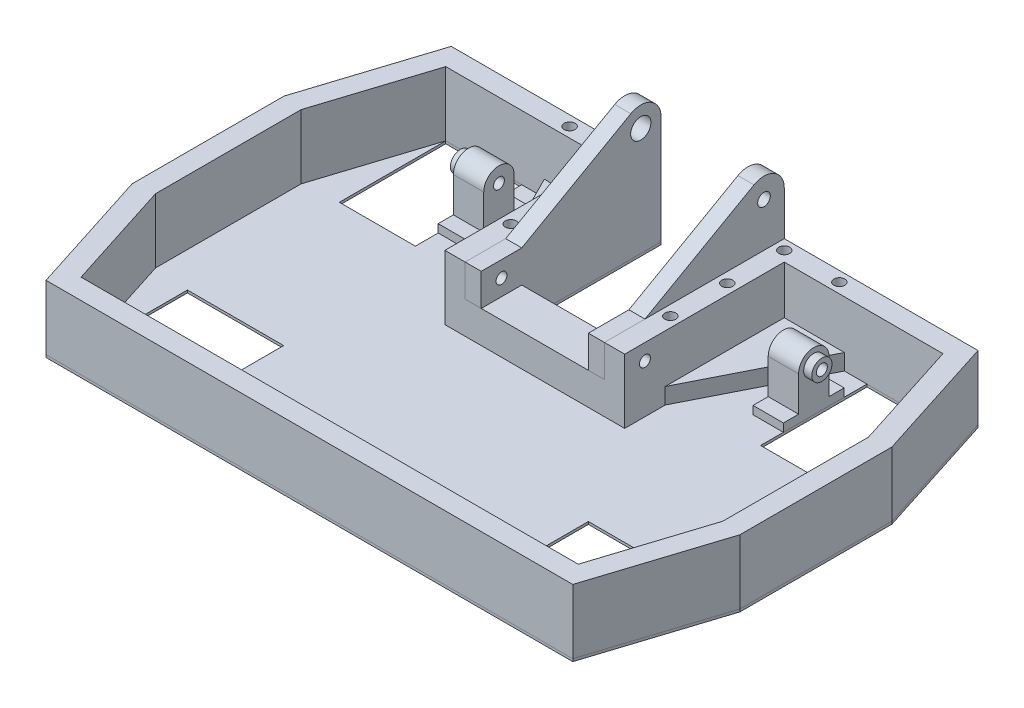
SolidWorks part; units mm, degrees
ref_plane "Front Plane" through (0, 0, 0) normal (0, 0, 1) x (1, 0, 0)
ref_plane "Top Plane" through (0, 0, 0) normal (0, 1, 0) x (1, 0, 0)
ref_plane "Right Plane" through (0, 0, 0) normal (1, 0, 0) x (0, 0, -1)
sketch "Sketch1" plane through (0, 0, 0) normal (0, 1, 0) x (1, 0, 0)
  line L0 (-27.5, 0) -> (-104, 0)
  line L1 (-104, 0) -> (-120, -50)
  line L2 (-120, -50) -> (-120, -110)
  line L3 (-120, -110) -> (-104, -160)
  line L4 (-104, -160) -> (104, -160)
  line L5 (104, -160) -> (120, -110)
  line L6 (120, -110) -> (120, -50)
  line L7 (120, -50) -> (104, 0)
  line L8 (104, 0) -> (27.5, 0)
  line L9 (-27.5, 0) -> (-27.5, -55)
  line L10 (27.5, 0) -> (27.5, -55)
  line L11 (-27.5, -55) -> (27.5, -55)
  line L13 (0, -51.275) -> (0, 31.275) construction
  point P16 (0, -160)
  point P17 (0, -10)
  dimension "D1" = 240
  dimension "D2" = 160
  dimension "D3" = 60
  dimension "D4" = 16
  dimension "D5" = 55
  dimension "D6" = 55
  dimension "D8" = 10
  dimension "D9" = 82.55
extrude "Extrude-Thin1" add sketch "Sketch1" along normal blind 25.4 thin thin type one direction reverse wall 8
sketch "Sketch19" plane through (0, 0, 0) normal (0, 0, -1) x (-1, 0, 0)
  line L0 (-21.15, 0) -> (-21.15, 50.8)
  line L1 (-27.5, 0) -> (27.5, 0) construction
  line L2 (-21.15, 50.8) -> (-27.5, 50.8)
  line L3 (-27.5, 50.8) -> (-27.5, 6.35)
  line L4 (-27.5, 6.35) -> (-59.25, 6.35)
  line L5 (-59.25, 6.35) -> (-59.25, 0)
  line L6 (-104, 0) -> (-27.5, 0) construction
  line L7 (-59.25, 0) -> (-21.15, 0)
  line L8 (-27.5, 25.4) -> (-27.5, 0) construction
  line L9 (0, 0) -> (0, 43.8117) construction
  line L10 (59.25, 0) -> (21.15, 0)
  line L11 (59.25, 6.35) -> (59.25, 0)
  line L12 (27.5, 6.35) -> (59.25, 6.35)
  line L13 (27.5, 50.8) -> (27.5, 6.35)
  line L14 (21.15, 50.8) -> (27.5, 50.8)
  line L15 (21.15, 0) -> (21.15, 50.8)
  dimension "D1" = 6.35
  dimension "D2" = 38.1
  dimension "D3" = 50.8
extrude "Cut-Extrude17" cut sketch "Sketch19" against normal up to surface (55 mm away) up to face at (0, 12.7, 55)
extrude "Boss-Extrude3" add sketch "Sketch19<2>" against normal up to surface (55 mm away) separate body
sketch "Sketch19<2>" plane through (0, 0, 0) normal (0, 0, -1) x (-1, 0, 0) same geometry as "Sketch19"
sketch "Sketch20" plane through (0, 6.35, 0) normal (0, 1, 0) x (1, 0, 0)
  line L0 (59.25, -8) -> (35.5, -55)
  line L1 (35.5, -55) -> (59.25, -55)
  line L2 (59.25, -55) -> (59.25, -8)
  line L3 (-35.5, -55) -> (-59.25, -8)
  line L4 (-59.25, -8) -> (-59.25, -55)
  line L5 (-59.25, -55) -> (-35.5, -55)
extrude "Cut-Extrude18" cut sketch "Sketch20" against normal through all
sketch "Sketch21" plane through (-27.5, 0, 0) normal (-1, 0, 0) x (0, 0, 1)
  line L0 (55, 25.4) -> (11.9382, 49.7535)
  line L1 (0, 6.35) -> (0, 50.8) construction
  line L2 (55, 50.8) -> (0, 50.8) construction
  line L3 (55, 25.4) -> (55, 58.9072)
  line L4 (55, 58.9072) -> (0, 58.9072)
  line L5 (0, 58.9072) -> (0, 42.79)
  arc A0 (11.9382, 49.7535) -> (0, 42.79) centre (8, 42.79) ccw
  circle A1 centre (8, 42.79) radius 2.5
  dimension "D1" = 8.01
  dimension "D3" = 5
  dimension "D2" = 8
extrude "Cut-Extrude20" cut sketch "Sketch21" against normal through all
sketch "Sketch22" plane through (0, 25.4, 0) normal (0, 1, 0) x (1, 0, 0)
  line L0 (35.5, -63) -> (-35.5, -63) construction
  line L1 (-27.5, -55) -> (27.5, -55)
  line L2 (-27.5, -55) -> (-27.5, -63)
  line L3 (-27.5, -63) -> (27.5, -63)
  line L4 (27.5, -55) -> (27.5, -63)
extrude "Cut-Extrude21" cut sketch "Sketch22" against normal blind 12.7
sketch "Sketch23" plane through (0, 0, 63) normal (0, 0, 1) x (1, 0, 0)
  line L8 (-27.5, 12.7) -> (-27.5, 25.4)
  line L9 (-27.5, 25.4) -> (-35.5, 25.4)
  line L10 (-35.5, 25.4) -> (-35.5, 0)
  line L11 (-35.5, 0) -> (35.5, 0)
  line L12 (35.5, 0) -> (35.5, 25.4)
  line L13 (35.5, 25.4) -> (27.5, 25.4)
  line L14 (27.5, 25.4) -> (27.5, 12.7)
  line L15 (27.5, 12.7) -> (-27.5, 12.7)
  line L16 (-27.5, 12.7) -> (-27.5, 25.4)
  line L17 (-27.5, 25.4) -> (-35.5, 25.4)
  line L18 (-35.5, 25.4) -> (-35.5, 0)
  line L19 (-35.5, 0) -> (35.5, 0)
  line L20 (35.5, 0) -> (35.5, 25.4)
  line L21 (35.5, 25.4) -> (27.5, 25.4)
  line L22 (27.5, 25.4) -> (27.5, 12.7)
  line L23 (27.5, 12.7) -> (-27.5, 12.7)
  dimension "D1" = 0
extrude "Boss-Extrude4" add sketch "Sketch23" along normal blind 8
sketch "Sketch24" plane through (0, 0, 55) normal (0, 0, 1) x (1, 0, 0)
  line L0 (-21.15, 25.4) -> (-21.15, 0) construction
  line L1 (-21.15, 12.7) -> (-27.5, 12.7)
  line L2 (-21.15, 12.7) -> (-21.15, 25.4)
  line L3 (-21.15, 25.4) -> (-27.5, 25.4)
  line L4 (-27.5, 12.7) -> (-27.5, 25.4)
  line L5 (21.15, 0) -> (21.15, 25.4) construction
  line L6 (21.15, 12.7) -> (27.5, 12.7)
  line L7 (21.15, 12.7) -> (21.15, 25.4)
  line L8 (21.15, 25.4) -> (27.5, 25.4)
  line L9 (27.5, 12.7) -> (27.5, 25.4)
extrude "Boss-Extrude5" add sketch "Sketch24" along normal up to surface (16 mm away) up to face at (0, 15.875, 71)
sketch "Sketch25" plane through (0, 0, 0) normal (0, -1, 0) x (1, 0, 0)
  line L0 (-104, 0) -> (-21.15, 0)
  line L1 (-21.15, 0) -> (-21.15, 55)
  line L2 (-21.15, 55) -> (21.15, 55)
  line L3 (21.15, 55) -> (21.15, 0)
  line L4 (21.15, 0) -> (104, 0)
  line L20 (-104, 0) -> (-59.25, 0)
  line L21 (-59.25, 0) -> (-59.25, 8)
  line L22 (-59.25, 8) -> (-98.1604, 8)
  line L23 (-98.1604, 8) -> (-112, 51.2488)
  line L24 (-112, 51.2488) -> (-112, 108.7512)
  line L25 (-112, 108.7512) -> (-98.1604, 152)
  line L26 (-98.1604, 152) -> (98.1604, 152)
  line L27 (98.1604, 152) -> (112, 108.7512)
  line L28 (112, 108.7512) -> (112, 51.2488)
  line L29 (112, 51.2488) -> (98.1604, 8)
  line L30 (98.1604, 8) -> (59.25, 8)
  line L31 (59.25, 8) -> (59.25, 0)
  line L32 (59.25, 0) -> (104, 0)
  line L33 (104, 0) -> (120, 50)
  line L34 (120, 50) -> (120, 110)
  line L35 (120, 110) -> (104, 160)
  line L36 (104, 160) -> (-104, 160)
  line L37 (-104, 160) -> (-120, 110)
  line L38 (-120, 110) -> (-120, 50)
  line L39 (-120, 50) -> (-104, 0)
  line L53 (104, 0) -> (120, 50)
  line L54 (120, 50) -> (120, 110)
  line L55 (120, 110) -> (104, 160)
  line L56 (104, 160) -> (-104, 160)
  line L57 (-104, 160) -> (-120, 110)
  line L58 (-120, 110) -> (-120, 50)
  line L59 (-120, 50) -> (-104, 0)
  dimension "D1" = 0
extrude "Boss-Extrude6" add sketch "Sketch25" along normal blind 1 separate body
sketch "Sketch26" plane through (-21.15, 0, 0) normal (1, 0, 0) x (0, 0, -1)
  circle A0 centre (-8, 42.79) radius 4
  dimension "D1" = 8
extrude "Cut-Extrude22" cut sketch "Sketch26" against normal through all
sketch "Sketch27" plane through (-21.15, 0, 0) normal (1, 0, 0) x (0, 0, -1)
  line L0 (-71, 12.7) -> (-55, 25.4) construction
  circle A0 centre (-63, 19.05) radius 2.159
  dimension "D1" = 4.318
extrude "Cut-Extrude23" cut sketch "Sketch27" against normal blind 31.5875 and the other way blind 61.5875
sketch "Sketch28" plane through (0, 0, 0) normal (0, 1, 0) x (1, 0, 0)
  line L0 (-112, -108.7512) -> (-98.1604, -152) construction
  line L1 (-98.1604, -8) -> (-68.1604, -8)
  line L2 (-98.1604, -8) -> (-98.1604, -50)
  line L3 (-98.1604, -50) -> (-68.1604, -50)
  line L4 (-68.1604, -8) -> (-68.1604, -50)
  line L5 (-98.1604, -152) -> (-60.1604, -152)
  line L6 (-98.1604, -152) -> (-98.1604, -110)
  line L7 (-98.1604, -110) -> (-60.1604, -110)
  line L8 (-60.1604, -152) -> (-60.1604, -110)
  line L9 (-98.1604, -152) -> (98.1604, -152) construction
  line L10 (98.1604, -152) -> (60.1604, -152)
  line L11 (98.1604, -152) -> (98.1604, -110)
  line L12 (98.1604, -110) -> (60.1604, -110)
  line L13 (60.1604, -152) -> (60.1604, -110)
  line L14 (98.1604, -8) -> (68.1604, -8)
  line L15 (98.1604, -8) -> (98.1604, -50)
  line L16 (98.1604, -50) -> (68.1604, -50)
  line L17 (68.1604, -8) -> (68.1604, -50)
  point P20 (57.9371, -110)
  dimension "D1" = 30
  dimension "D2" = 42
  dimension "D3" = 8
extrude "Cut-Extrude24" cut sketch "Sketch28" against normal blind 31.5875
sketch "Sketch29" plane through (0, 25.4, 0) normal (0, 1, 0) x (1, 0, 0)
  line L0 (-83.4506, -8) -> (-83.4506, 0) construction
  line L1 (-35.5, -8) -> (-98.1604, -8) construction
  line L2 (-27.5, 0) -> (-104, 0) construction
  line L3 (-27.5, -71) -> (-35.5, -71) construction
  line L4 (-31.5, -4) -> (-31.5, -49) construction
  line L5 (0, 0) -> (0, -23.7972) construction
  line L6 (31.5, -4) -> (31.5, -49) construction
  circle A0 centre (-31.5, -49) radius 2.159
  circle A1 centre (-31.5, -26.5) radius 2.159
  circle A2 centre (-31.5, -4) radius 2.159
  circle A3 centre (-53.25, -4) radius 2.159
  circle A5 centre (53.25, -4) radius 2.159
  circle A6 centre (31.5, -4) radius 2.159
  circle A7 centre (31.5, -26.5) radius 2.159
  circle A8 centre (31.5, -49) radius 2.159
  point P14 (-83.4506, -4)
  point P17 (-31.5, -71)
  dimension "D1" = 6
  dimension "D3" = 4.318
  dimension "D2" = 6
extrude "Cut-Extrude25" cut sketch "Sketch29" against normal blind 31.5875
sketch "Sketch30" plane through (-68.1604, 0, 0) normal (-1, 0, 0) x (0, 0, 1)
  line L0 (50, 0) -> (8, 0) construction
  line L1 (41, 0) -> (17, 0)
  line L2 (41, 0) -> (41, 3.2)
  line L3 (41, 3.2) -> (35, 3.2)
  line L4 (17, 0) -> (17, 3.2)
  line L5 (23, 3.2) -> (23, 17)
  line L6 (35, 17) -> (35, 3.2)
  line L7 (23, 3.2) -> (17, 3.2)
  line L8 (8, -1) -> (50, -1) construction
  line L9 (50, -1) -> (0, -1) construction
  arc A0 (23, 17) -> (35, 17) centre (29, 17) cw
  circle A1 centre (29, 17) radius 2.159
  circle A2 centre (29, 17) radius 21 construction
  point P12 (29, -4)
  point P15 (29, -1)
  dimension "D1" = 4.318
  dimension "D2" = 6
  dimension "D5" = 42
  dimension "D3" = 6
  dimension "D4" = 3.2
  dimension "D6" = 3
extrude "Boss-Extrude7" add sketch "Sketch30" against normal blind 12 separate body
sketch "Sketch33" plane through (-68.1604, 0, 0) normal (-1, 0, 0) x (0, 0, 1)
  circle A0 centre (29, 17) radius 2.159
  circle A1 centre (29, 17) radius 4
  dimension "D1" = 8
extrude "Boss-Extrude9" add sketch "Sketch33" along normal blind 3.2
mirror "Mirror2" about plane through (0, 0, 0) normal (1, 0, 0) of bodies 173 167
ref_plane "Plane1" through (0, 0, 80) normal (0, 0, -1) x (-1, 0, 0)
sketch "Sketch31" plane through (-21.15, 0, 0) normal (1, 0, 0) x (0, 0, -1)
  line L0 (-69.6118, 49.4909) -> (-13.8539, 64.5151)
  line L1 (-65.6357, 20.0077) -> (-7.8899, 20.2903)
  line L2 (-25.7091, 83.6306) -> (-160, 25.4) construction
  circle A0 centre (-8, 42.79) radius 22.5
  circle A1 centre (-65.7091, 35.0075) radius 15
  circle A2 centre (-65.7091, 35.0075) radius 20
  circle A3 centre (-8, 42.79) radius 44.5148
  dimension "D1" = 40
  dimension "D2" = 30
  dimension "D3" = 45
